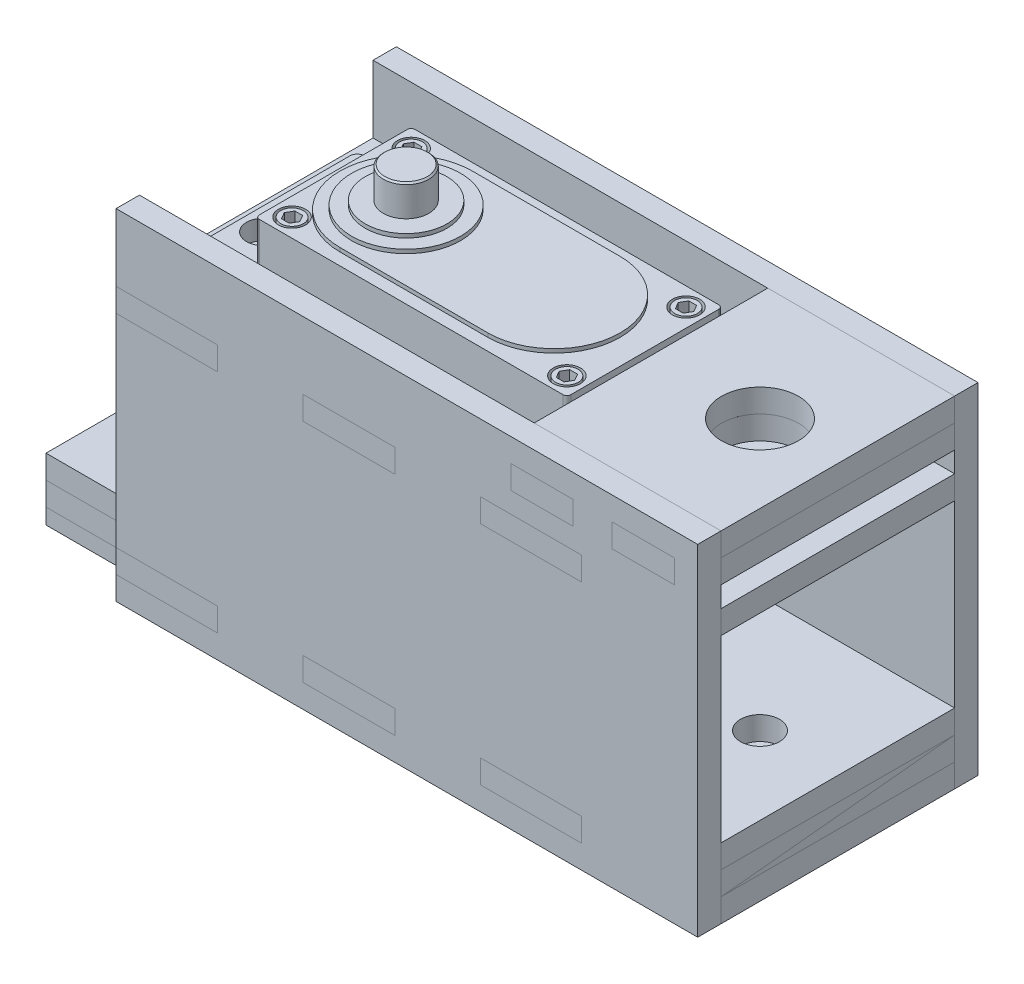
SolidWorks part; units mm, degrees
ref_plane "前视基准面" through (0, 0, 0) normal (0, 0, 1) x (1, 0, 0)
ref_plane "上视基准面" through (0, 0, 0) normal (0, 1, 0) x (1, 0, 0)
ref_plane "右视基准面" through (0, 0, 0) normal (1, 0, 0) x (0, 0, -1)
sketch "草图1" plane through (0, 0, 0) normal (0, 0, 1) x (1, 0, 0)
  line L1 (-20, -18.85) -> (20, -18.85)
  line L2 (-20, -18.85) -> (-20, 18.85)
  line L3 (-20, 18.85) -> (20, 18.85)
  line L4 (20, -18.85) -> (20, 18.85)
  line L5 (-20, -18.85) -> (20, 18.85) construction
  line L6 (-20, 18.85) -> (20, -18.85) construction
  point P0 (0, 0)
  dimension "D1" = 37.7
  dimension "D2" = 40
extrude "凸台-拉伸1" add sketch "草图1" along normal blind 20
sketch "草图2" plane through (0, 18.85, 0) normal (0, 1, 0) x (1, 0, 0)
  line L0 (-20, -20) -> (-20, 0) construction
  line L1 (20, 0) -> (-20, 0) construction
  line L2 (0, 0) -> (0, -4.2518) construction
  line L3 (20, -10) -> (9.0138, -10) construction
  line L4 (20, -20) -> (20, 0) construction
  circle A0 centre (-17.65, -2.35) radius 1.75
  circle A1 centre (17.65, -2.35) radius 1.75
  circle A2 centre (17.65, -17.65) radius 1.75
  circle A3 centre (-17.65, -17.65) radius 1.75
  dimension "D1" = 3.5
  dimension "D2" = 2.35
  dimension "D3" = 2.35
extrude "切除-拉伸1" cut sketch "草图2" against normal blind 1.5 contours A0 | A1 | A2 | A3
sketch "草图3" plane through (0, 17.35, 0) normal (0, 1, 0) x (1, 0, 0)
  line L0 (0, 0) -> (0, -10.9401) construction
  line L1 (-17.15, -1.484) -> (-18.15, -1.484)
  line L2 (-18.15, -1.484) -> (-18.65, -2.35)
  line L3 (-18.65, -2.35) -> (-18.15, -3.216)
  line L4 (-18.15, -3.216) -> (-17.15, -3.216)
  line L5 (-17.15, -3.216) -> (-16.65, -2.35)
  line L6 (-16.65, -2.35) -> (-17.15, -1.484)
  line L7 (20, 0) -> (-20, 0) construction
  line L8 (-20, -10) -> (-14.6951, -10) construction
  line L9 (-20, -20) -> (-20, 0) construction
  line L10 (-17.15, -18.516) -> (-18.15, -18.516)
  line L11 (-16.65, -17.65) -> (-17.15, -18.516)
  line L12 (-17.15, -16.784) -> (-16.65, -17.65)
  line L13 (-18.15, -16.784) -> (-17.15, -16.784)
  line L14 (-18.65, -17.65) -> (-18.15, -16.784)
  line L15 (-18.15, -18.516) -> (-18.65, -17.65)
  line L16 (16.65, -17.65) -> (17.15, -18.516)
  line L17 (17.15, -16.784) -> (16.65, -17.65)
  line L18 (18.15, -16.784) -> (17.15, -16.784)
  line L19 (18.65, -17.65) -> (18.15, -16.784)
  line L20 (18.15, -18.516) -> (18.65, -17.65)
  line L21 (17.15, -18.516) -> (18.15, -18.516)
  line L22 (16.65, -2.35) -> (17.15, -1.484)
  line L23 (17.15, -3.216) -> (16.65, -2.35)
  line L24 (17.15, -1.484) -> (18.15, -1.484)
  line L25 (18.15, -1.484) -> (18.65, -2.35)
  line L26 (18.65, -2.35) -> (18.15, -3.216)
  line L27 (18.15, -3.216) -> (17.15, -3.216)
  circle A2 centre (-17.65, -2.35) radius 1.45
  circle A3 centre (-17.65, -2.35) radius 1.45
  circle A4 centre (-17.65, -17.65) radius 1.45
  circle A5 centre (17.65, -2.35) radius 1.45
  circle A6 centre (17.65, -2.35) radius 1.45
  circle A7 centre (-17.65, -17.65) radius 1.45
  circle A8 centre (-17.65, -2.35) radius 0.866 construction
  circle A9 centre (17.65, -17.65) radius 1.45
  circle A10 centre (17.65, -17.65) radius 1.45
  dimension "D5" = 1
  dimension "D1" = 0.3
  dimension "D2" = 0.3
  dimension "D3" = 0.3
  dimension "D4" = 0.3
extrude "凸台-拉伸2" add sketch "草图3" along normal blind 1.5
sketch "草图4" plane through (0, 18.85, 0) normal (0, 1, 0) x (1, 0, 0)
  line L0 (-10.7, -9.95) -> (8.3, -9.95) construction
  line L1 (-10.7, -1.45) -> (8.3, -1.45)
  line L2 (-10.7, -18.45) -> (8.3, -18.45)
  line L3 (20, 0) -> (-20, 0) construction
  line L4 (20, -20) -> (-20, -20) construction
  line L5 (-20, -20) -> (-20, 0) construction
  arc A0 (-10.7, -1.45) -> (-10.7, -18.45) centre (-10.7, -9.95) ccw
  arc A1 (8.3, -18.45) -> (8.3, -1.45) centre (8.3, -9.95) ccw
  point P2 (-1.2, -9.95)
  dimension "D1" = 17
  dimension "D2" = 1.45
  dimension "D3" = 1.55
  dimension "D4" = 19
  dimension "D5" = 9.3
extrude "凸台-拉伸3" add sketch "草图4" along normal blind 0.5
sketch "草图5" plane through (0, 19.35, 0) normal (0, 1, 0) x (1, 0, 0)
  circle A0 centre (-10.7, -9.95) radius 7
  dimension "D1" = 14
extrude "凸台-拉伸4" add sketch "草图5" along normal blind 0.5
sketch "草图6" plane through (0, 19.85, 0) normal (0, 1, 0) x (1, 0, 0)
  circle A0 centre (-10.7, -9.95) radius 5.25
  dimension "D1" = 10.5
extrude "凸台-拉伸5" add sketch "草图6" along normal blind 0.5
sketch "草图7" plane through (0, 20.35, 0) normal (0, 1, 0) x (1, 0, 0)
  circle A0 centre (-10.7, -9.95) radius 2.925
  dimension "D1" = 5.85
extrude "凸台-拉伸6" add sketch "草图7" along normal blind 4
chamfer "倒角1" distance 0.2 angle 45 1 edges at (-10.7, 24.35, 12.875)
sketch "草图8" plane through (0, 0, 20) normal (0, 0, 1) x (1, 0, 0)
  line L0 (20, -18.85) -> (20, 18.85) construction
  line L1 (-26.9, 12.7) -> (26.9, 12.7)
  line L2 (-26.9, 12.7) -> (-26.9, 10.2)
  line L3 (-26.9, 10.2) -> (26.9, 10.2)
  line L4 (26.9, 12.7) -> (26.9, 10.2)
  line L5 (-20, 18.85) -> (-20, -18.85) construction
  dimension "D1" = 2.5
  dimension "D2" = 6.15
  dimension "D3" = 6.9
  dimension "D4" = 6.9
extrude "凸台-拉伸7" add sketch "草图8" against normal up to surface (20 mm away) up to face at (0, 0, 0)
ref_plane "基准面1" through (0, 0, 0) normal (0, 1, 0) x (1, 0, 0)
mirror "镜向1" about plane through (0, 0, 0) normal (0, 1, 0) of "凸台-拉伸2", "切除-拉伸1"
fillet "圆角1" radius 1 4 edges at (-26.9, 11.45, 20) (-26.9, 11.45, 0) (26.9, 11.45, 0) (26.9, 11.45, 20)
sketch "草图9" plane through (0, 12.7, 0) normal (0, 1, 0) x (1, 0, 0)
  line L0 (-20, -20) -> (-25.9, -20) construction
  line L1 (-20, 0) -> (-20, -20) construction
  line L2 (-20, 0) -> (-25.9, 0) construction
  line L3 (0, 0) -> (0, -21.9377) construction
  circle A0 centre (-24, -5) radius 2.15
  circle A1 centre (-24, -15) radius 2.15
  circle A2 centre (24, -15) radius 2.15
  circle A3 centre (24, -5) radius 2.15
  dimension "D1" = 4.3
  dimension "D2" = 4.3
  dimension "D3" = 5
  dimension "D4" = 4
  dimension "D5" = 5
  dimension "D6" = 4
extrude "切除-拉伸2" cut sketch "草图9" against normal blind 4 contours A1 | A0 | A2 | A3
fillet "圆角2" radius 0.5 8 edges at (-20, 15.775, 0) (20, 15.775, 0) (20, -4.325, 0) (-20, -4.325, 0) (-20, -4.325, 20) (-20, 15.775, 20) (20, -4.325, 20) (20, 15.775, 20)
sketch "草图10" plane through (0, 10.2, 0) normal (0, -1, 0) x (1, 0, 0)
  line L0 (-19.5, 20) -> (19.5, 20) construction
  line L1 (-41.9, -5) -> (41.9, -5)
  line L2 (-41.9, -5) -> (-41.9, 25)
  line L3 (-41.9, 25) -> (41.9, 25)
  line L4 (41.9, -5) -> (41.9, 25)
  line L5 (-41.9, -5) -> (41.9, 25) construction
  line L6 (-41.9, 25) -> (41.9, -5) construction
  line L7 (-19.5, 0) -> (19.5, 0) construction
  line L8 (-26.9, 1) -> (-26.9, 19) construction
  line L9 (26.9, 1) -> (26.9, 19) construction
  line L10 (20, 19.5) -> (20, 0.5) construction
  line L11 (-20, 19.5) -> (-20, 0.5) construction
  line L12 (20, 19.5) -> (20, 0.5)
  line L13 (-19.5, 0) -> (19.5, 0)
  line L14 (-20, 19.5) -> (-20, 0.5)
  line L15 (-19.5, 20) -> (19.5, 20)
  arc A8 (20, 19.5) -> (19.5, 20) centre (19.5, 19.5) ccw construction
  arc A9 (19.5, 0) -> (20, 0.5) centre (19.5, 0.5) ccw construction
  arc A10 (-20, 0.5) -> (-19.5, 0) centre (-19.5, 0.5) ccw construction
  arc A11 (-19.5, 20) -> (-20, 19.5) centre (-19.5, 19.5) ccw construction
  arc A12 (20, 19.5) -> (19.5, 20) centre (19.5, 19.5) ccw
  arc A13 (19.5, 0) -> (20, 0.5) centre (19.5, 0.5) ccw
  arc A14 (-20, 0.5) -> (-19.5, 0) centre (-19.5, 0.5) ccw
  arc A15 (-19.5, 20) -> (-20, 19.5) centre (-19.5, 19.5) ccw
  circle A16 centre (-24, 15) radius 1.25
  circle A17 centre (-24, 5) radius 1.25
  circle A18 centre (24, 5) radius 1.25
  circle A19 centre (24, 15) radius 1.25
  point P0 (0, 10)
  dimension "D5" = 2.5
  dimension "D6" = 2.5
  dimension "D7" = 2.5
  dimension "D8" = 2.5
  dimension "D1" = 5
  dimension "D2" = 5
  dimension "D3" = 15
  dimension "D4" = 15
extrude "凸台-拉伸8" add sketch "草图10" along normal blind 3 separate body
sketch "草图11" plane through (0, 0, -5) normal (0, 0, -1) x (-1, 0, 0)
  line L0 (41.9, 10.2) -> (-41.9, 10.2) construction
  line L1 (-29.9, 10.2) -> (-16.9, 10.2)
  line L2 (-29.9, 10.2) -> (-29.9, 7.2)
  line L3 (-29.9, 7.2) -> (-16.9, 7.2)
  line L4 (-16.9, 10.2) -> (-16.9, 7.2)
  line L5 (41.9, 7.2) -> (-41.9, 7.2) construction
  line L6 (-41.9, 7.2) -> (-41.9, 10.2) construction
  line L11 (16.9, 10.2) -> (29.9, 10.2)
  line L12 (16.9, 10.2) -> (16.9, 7.2)
  line L13 (16.9, 7.2) -> (29.9, 7.2)
  line L14 (29.9, 10.2) -> (29.9, 7.2)
  line L15 (-5.9, 10.2) -> (5.9, 10.2)
  line L16 (-5.9, 10.2) -> (-5.9, 7.2)
  line L17 (-5.9, 7.2) -> (5.9, 7.2)
  line L18 (5.9, 10.2) -> (5.9, 7.2)
  line L19 (41.9, 7.2) -> (41.9, 10.2) construction
  dimension "D1" = 13
  dimension "D2" = 11
  dimension "D3" = 13
  dimension "D4" = 12
  dimension "D5" = 12
  dimension "D6" = 11
extrude "凸台-拉伸9" add sketch "草图11" along normal blind 3
ref_plane "基准面2" through (0, 0, 10) normal (0, 0, -1) x (-1, 0, 0)
mirror "镜向2" about plane through (0, 0, 10) normal (0, 0, -1) of "凸台-拉伸9"
sketch "草图14" plane through (0, 0, -5) normal (0, 0, -1) x (-1, 0, 0)
  line L0 (41.9, 7.2) -> (41.9, 10.2) construction
  line L1 (-41.9, 18.85) -> (41.9, 18.85)
  line L2 (-41.9, 18.85) -> (-41.9, -23.85)
  line L3 (-41.9, -23.85) -> (41.9, -23.85)
  line L4 (41.9, 18.85) -> (41.9, -23.85)
  line L5 (-19.5, 18.85) -> (19.5, 18.85) construction
  line L6 (-41.9, 7.2) -> (-41.9, 10.2) construction
  line L7 (16.9, 10.2) -> (16.9, 7.2) construction
  line L8 (16.9, 7.2) -> (29.9, 7.2) construction
  line L9 (29.9, 7.2) -> (29.9, 10.2) construction
  line L10 (29.9, 10.2) -> (16.9, 10.2) construction
  line L11 (-5.9, 10.2) -> (-5.9, 7.2) construction
  line L12 (-5.9, 7.2) -> (5.9, 7.2) construction
  line L13 (5.9, 7.2) -> (5.9, 10.2) construction
  line L14 (5.9, 10.2) -> (-5.9, 10.2) construction
  line L15 (-29.9, 10.2) -> (-29.9, 7.2) construction
  line L16 (-29.9, 7.2) -> (-16.9, 7.2) construction
  line L17 (-16.9, 7.2) -> (-16.9, 10.2) construction
  line L18 (-16.9, 10.2) -> (-29.9, 10.2) construction
  line L19 (16.9, 10.2) -> (16.9, 7.2)
  line L20 (16.9, 7.2) -> (29.9, 7.2)
  line L21 (29.9, 7.2) -> (29.9, 10.2)
  line L22 (29.9, 10.2) -> (16.9, 10.2)
  line L23 (-5.9, 10.2) -> (-5.9, 7.2)
  line L24 (-5.9, 7.2) -> (5.9, 7.2)
  line L25 (5.9, 7.2) -> (5.9, 10.2)
  line L26 (5.9, 10.2) -> (-5.9, 10.2)
  line L27 (-29.9, 10.2) -> (-29.9, 7.2)
  line L28 (-29.9, 7.2) -> (-16.9, 7.2)
  line L29 (-16.9, 7.2) -> (-16.9, 10.2)
  line L30 (-16.9, 10.2) -> (-29.9, 10.2)
  line L31 (19.5, -18.85) -> (-19.5, -18.85) construction
  dimension "D1" = 0
  dimension "D2" = 0
  dimension "D3" = 0
  dimension "D4" = 5
extrude "凸台-拉伸10" add sketch "草图14" along normal blind 3 separate body
mirror "镜向3" about plane through (0, 0, 10) normal (0, 0, -1) of bodies 119
sketch "草图15" plane through (41.9, 0, 0) normal (1, 0, 0) x (0, 0, -1)
  line L4 (5, 10.2) -> (-25, 10.2)
  line L5 (-25, 10.2) -> (-25, 7.2)
  line L6 (-25, 7.2) -> (5, 7.2)
  line L7 (5, 7.2) -> (5, 10.2)
  line L8 (5, 10.2) -> (-25, 10.2)
  line L9 (-25, 10.2) -> (-25, 7.2)
  line L10 (-25, 7.2) -> (5, 7.2)
  line L11 (5, 7.2) -> (5, 10.2)
  dimension "D1" = 0
extrude "凸台-拉伸11" add sketch "草图15" along normal blind 15
sketch "草图16" plane through (41.9, 0, 0) normal (1, 0, 0) x (0, 0, -1)
  line L4 (5, 18.85) -> (5, -23.85)
  line L5 (5, -23.85) -> (8, -23.85)
  line L6 (8, -23.85) -> (8, 18.85)
  line L7 (8, 18.85) -> (5, 18.85)
  line L8 (5, 18.85) -> (5, -23.85)
  line L9 (5, -23.85) -> (8, -23.85)
  line L10 (8, -23.85) -> (8, 18.85)
  line L11 (8, 18.85) -> (5, 18.85)
  dimension "D1" = 0
extrude "凸台-拉伸12" add sketch "草图16" along normal up to surface (15 mm away) up to face at (56.9, 8.7, 10)
sketch "草图17" plane through (41.9, 0, 0) normal (1, 0, 0) x (0, 0, -1)
  line L4 (-25, -23.85) -> (-25, 18.85)
  line L5 (-25, 18.85) -> (-28, 18.85)
  line L6 (-28, 18.85) -> (-28, -23.85)
  line L7 (-28, -23.85) -> (-25, -23.85)
  line L8 (-25, -23.85) -> (-25, 18.85)
  line L9 (-25, 18.85) -> (-28, 18.85)
  line L10 (-28, 18.85) -> (-28, -23.85)
  line L11 (-28, -23.85) -> (-25, -23.85)
  dimension "D1" = 0
extrude "凸台-拉伸13" add sketch "草图17" along normal up to surface (15 mm away) up to face at (56.9, 8.7, 10)
sketch "草图18" plane through (0, 10.2, 0) normal (0, 1, 0) x (1, 0, 0)
  line L0 (26.9, -1) -> (26.9, -19) construction
  circle A0 centre (52.3, -10) radius 2.5
  dimension "D2" = 5
  dimension "D1" = 25.4
extrude "切除-拉伸3" cut sketch "草图18" against normal blind 15
sketch "草图19" plane through (0, 18.85, 0) normal (0, 1, 0) x (1, 0, 0)
  line L0 (29.9, 5) -> (56.9, 5) construction
  line L1 (56.9, 8) -> (31.9, 8)
  line L2 (56.9, 8) -> (56.9, 5)
  line L3 (56.9, 5) -> (31.9, 5)
  line L4 (31.9, 8) -> (31.9, 5)
  dimension "D1" = 25
extrude "凸台-拉伸14" add sketch "草图19" along normal blind 8
sketch "草图20" plane through (0, 18.85, 0) normal (0, 1, 0) x (1, 0, 0)
  line L0 (56.9, -25) -> (29.9, -25) construction
  line L1 (31.9, -25) -> (56.9, -25)
  line L2 (31.9, -25) -> (31.9, -28)
  line L3 (31.9, -28) -> (56.9, -28)
  line L4 (56.9, -25) -> (56.9, -28)
extrude "凸台-拉伸15" add sketch "草图20" along normal up to surface (8 mm away) up to face at (44.4, 26.85, -6.5)
sketch "草图21" plane through (56.9, 0, 0) normal (1, 0, 0) x (0, 0, -1)
  line L0 (-25, 26.85) -> (-28, 26.85) construction
  line L1 (-25, 26.85) -> (5, 26.85)
  line L2 (-25, 26.85) -> (-25, 23.85)
  line L3 (-25, 23.85) -> (5, 23.85)
  line L4 (5, 26.85) -> (5, 23.85)
  line L5 (5, 26.85) -> (5, -23.85) construction
  dimension "D1" = 3
extrude "凸台-拉伸16" add sketch "草图21" against normal up to surface (25 mm away) separate body up to face at (31.9, 22.85, 26.5)
sketch "草图22" plane through (0, 23.85, 0) normal (0, -1, 0) x (1, 0, 0)
  circle A0 centre (52.3, 10) radius 2.5 construction
  circle A1 centre (52.3, 10) radius 2.5
extrude "切除-拉伸4" cut sketch "草图22" against normal blind 10
sketch "草图23" plane through (0, 26.85, 0) normal (0, 1, 0) x (1, 0, 0)
  line L0 (12.837, -10) -> (-55.6494, -10) construction
  line L2 (56.9, -28) -> (31.9, -28) construction
  line L3 (56.9, 8) -> (31.9, 8) construction
  line L4 (56.9, -28) -> (47.6466, -28)
  line L5 (56.9, 8) -> (47.6466, 8)
  line L6 (56.9, 8) -> (79.2685, 8)
  line L7 (79.2685, 8) -> (56.9, -28)
  arc A0 (47.6466, -28) -> (47.6466, 8) centre (34.8957, -10) ccw
extrude "切除-拉伸5" cut sketch "草图23" against normal blind 100
sketch "草图25" plane through (0, -18.85, 0) normal (0, -1, 0) x (1, 0, 0)
  line L0 (-20, 19.5) -> (-20, 0.5) construction
  line L1 (-41.9, 25) -> (51.0693, 25)
  line L2 (-41.9, 25) -> (-41.9, -5)
  line L3 (-41.9, -5) -> (51.0693, -5)
  line L4 (51.0693, 25) -> (51.0693, -5)
  line L5 (-19.5, 20) -> (19.5, 20) construction
  line L6 (20, 19.5) -> (20, 0.5) construction
  line L7 (-19.5, 0) -> (19.5, 0) construction
  line L8 (-20, 19.5) -> (-20, 0.5)
  line L9 (-19.5, 20) -> (19.5, 20)
  line L10 (20, 19.5) -> (20, 0.5)
  line L11 (-19.5, 0) -> (19.5, 0)
  arc A0 (-20, 0.5) -> (-19.5, 0) centre (-19.5, 0.5) ccw construction
  arc A1 (-19.5, 20) -> (-20, 19.5) centre (-19.5, 19.5) ccw construction
  arc A2 (20, 19.5) -> (19.5, 20) centre (19.5, 19.5) ccw construction
  arc A3 (19.5, 0) -> (20, 0.5) centre (19.5, 0.5) ccw construction
  arc A4 (-20, 0.5) -> (-19.5, 0) centre (-19.5, 0.5) ccw
  arc A5 (-19.5, 20) -> (-20, 19.5) centre (-19.5, 19.5) ccw
  arc A6 (20, 19.5) -> (19.5, 20) centre (19.5, 19.5) ccw
  arc A7 (19.5, 0) -> (20, 0.5) centre (19.5, 0.5) ccw
extrude "凸台-拉伸17" add sketch "草图25" against normal blind 3 separate body
sketch "草图26" plane through (0, -18.85, 0) normal (0, -1, 0) x (1, 0, 0)
  line L0 (56.9, 11.5478) -> (56.9, 8.4522) construction
  line L1 (56.9, 11.5478) -> (56.9, 8.4522)
  line L2 (51.0693, -5) -> (51.0693, 25) construction
  line L3 (51.0693, -5) -> (51.0693, 25)
  arc A0 (51.0693, -5) -> (56.9, 8.4522) centre (34.8957, 10) ccw construction
  arc A1 (51.0693, -5) -> (56.9, 8.4522) centre (34.8957, 10) ccw
  arc A2 (56.9, 11.5478) -> (51.0693, 25) centre (34.8957, 10) ccw construction
  arc A3 (56.9, 11.5478) -> (51.0693, 25) centre (34.8957, 10) ccw
extrude "凸台-拉伸18" add sketch "草图26" against normal blind 3
sketch "草图27" plane through (0, -15.85, 0) normal (0, 1, 0) x (1, 0, 0)
  circle A0 centre (52.3, -10) radius 2.5 construction
  circle A1 centre (52.3, -10) radius 2.5
extrude "切除-拉伸6" cut sketch "草图27" against normal blind 3
sketch "草图28" plane through (0, -18.85, 0) normal (0, -1, 0) x (1, 0, 0)
  line L4 (-41.9, 25) -> (-41.9, -5)
  line L5 (-41.9, -5) -> (51.0693, -5)
  line L6 (56.9, 8.4522) -> (56.9, 11.5478)
  line L7 (51.0693, 25) -> (-41.9, 25)
  line L8 (-41.9, 25) -> (-41.9, -5)
  line L9 (-41.9, -5) -> (51.0693, -5)
  line L10 (56.9, 8.4522) -> (56.9, 11.5478)
  line L11 (51.0693, 25) -> (-41.9, 25)
  arc A2 (51.0693, -5) -> (56.9, 8.4522) centre (34.8957, 10) ccw
  arc A3 (56.9, 11.5478) -> (51.0693, 25) centre (34.8957, 10) ccw
  arc A4 (51.0693, -5) -> (56.9, 8.4522) centre (34.8957, 10) ccw
  arc A5 (56.9, 11.5478) -> (51.0693, 25) centre (34.8957, 10) ccw
  dimension "D1" = 0
extrude "凸台-拉伸19" add sketch "草图28" along normal up to surface (5 mm away) separate body
sketch "草图29" plane through (0, -18.85, 0) normal (0, 1, 0) x (1, 0, 0)
  circle A0 centre (52.3, -10) radius 2.5 construction
  circle A1 centre (52.3, -10) radius 2.5
extrude "切除-拉伸7" cut sketch "草图29" against normal blind 13
sketch "草图30" plane through (0, 26.85, 0) normal (0, 1, 0) x (1, 0, 0)
  line L2 (34.8, 20.7576) -> (34.8, -40.7576)
  line L3 (34.8, -40.7576) -> (61.8691, -40.7576)
  line L5 (34.8, 20.7576) -> (61.8691, 20.7576)
  line L6 (61.8691, -40.7576) -> (61.8691, 20.7576)
extrude "切除-拉伸8" cut sketch "草图30" against normal blind 76
sketch "草图31" plane through (34.8, 0, 0) normal (1, 0, 0) x (0, 0, -1)
  line L4 (-25, 26.85) -> (-25, 23.85)
  line L5 (-25, 23.85) -> (5, 23.85)
  line L6 (5, 23.85) -> (5, 26.85)
  line L7 (5, 26.85) -> (-25, 26.85)
  line L8 (-25, 26.85) -> (-25, 23.85)
  line L9 (-25, 23.85) -> (5, 23.85)
  line L10 (5, 23.85) -> (5, 26.85)
  line L11 (5, 26.85) -> (-25, 26.85)
  dimension "D1" = 0
extrude "凸台-拉伸20" add sketch "草图31" along normal blind 10
sketch "草图32" plane through (34.8, 0, 0) normal (1, 0, 0) x (0, 0, -1)
  line L4 (8, -23.85) -> (8, 26.85)
  line L5 (8, 26.85) -> (5, 26.85)
  line L6 (5, 26.85) -> (5, -23.85)
  line L7 (5, -23.85) -> (8, -23.85)
  line L8 (8, -23.85) -> (8, 26.85)
  line L9 (8, 26.85) -> (5, 26.85)
  line L10 (5, 26.85) -> (5, -23.85)
  line L11 (5, -23.85) -> (8, -23.85)
  dimension "D1" = 0
extrude "凸台-拉伸21" add sketch "草图32" along normal blind 10
sketch "草图33" plane through (34.8, 0, 0) normal (1, 0, 0) x (0, 0, -1)
  line L4 (-28, 26.85) -> (-28, -23.85)
  line L5 (-28, -23.85) -> (-25, -23.85)
  line L6 (-25, -23.85) -> (-25, 26.85)
  line L7 (-25, 26.85) -> (-28, 26.85)
  line L8 (-28, 26.85) -> (-28, -23.85)
  line L9 (-28, -23.85) -> (-25, -23.85)
  line L10 (-25, -23.85) -> (-25, 26.85)
  line L11 (-25, 26.85) -> (-28, 26.85)
  dimension "D1" = 0
extrude "凸台-拉伸22" add sketch "草图33" along normal blind 10
sketch "草图34" plane through (34.8, 0, 0) normal (1, 0, 0) x (0, 0, -1)
  line L4 (-25, 7.2) -> (5, 7.2)
  line L5 (5, 7.2) -> (5, 10.2)
  line L6 (5, 10.2) -> (-25, 10.2)
  line L7 (-25, 10.2) -> (-25, 7.2)
  line L8 (-25, 7.2) -> (5, 7.2)
  line L9 (5, 7.2) -> (5, 10.2)
  line L10 (5, 10.2) -> (-25, 10.2)
  line L11 (-25, 10.2) -> (-25, 7.2)
  dimension "D1" = 0
extrude "凸台-拉伸23" add sketch "草图34" along normal up to surface (10 mm away) up to face at (44.8, 25.35, 10)
sketch "草图35" plane through (34.8, 0, 0) normal (1, 0, 0) x (0, 0, -1)
  line L4 (-25, -15.85) -> (-25, -18.85)
  line L5 (-25, -18.85) -> (5, -18.85)
  line L6 (5, -18.85) -> (5, -15.85)
  line L7 (5, -15.85) -> (-25, -15.85)
  line L8 (-25, -15.85) -> (-25, -18.85)
  line L9 (-25, -18.85) -> (5, -18.85)
  line L10 (5, -18.85) -> (5, -15.85)
  line L11 (5, -15.85) -> (-25, -15.85)
  dimension "D1" = 0
extrude "凸台-拉伸24" add sketch "草图35" along normal blind 10
sketch "草图36" plane through (0, 26.85, 0) normal (0, 1, 0) x (1, 0, 0)
  line L0 (26.9, -10) -> (34.8, -10)
  line L1 (26.9, -1) -> (26.9, -19) construction
  circle A0 centre (34.8, -10) radius 2.5
  dimension "D2" = 5
  dimension "D1" = 7.9
extrude "切除-拉伸9" cut sketch "草图36" against normal blind 90 contours A0 region at (34.8, 26.85, 12.4293)
sketch "草图37" plane through (0, -18.85, 0) normal (0, -1, 0) x (1, 0, 0)
  line L4 (-41.9, -5) -> (44.8, -5)
  line L5 (44.8, -5) -> (44.8, 25)
  line L6 (44.8, 25) -> (-41.9, 25)
  line L7 (-41.9, 25) -> (-41.9, -5)
  line L8 (-41.9, -5) -> (44.8, -5)
  line L9 (44.8, -5) -> (44.8, 25)
  line L10 (44.8, 25) -> (-41.9, 25)
  line L11 (-41.9, 25) -> (-41.9, -5)
  dimension "D1" = 0
extrude "凸台-拉伸25" add sketch "草图37" along normal blind 3 separate body
sketch "草图38" plane through (0, -23.85, 0) normal (0, -1, 0) x (1, 0, 0)
  line L4 (-41.9, -8) -> (44.8, -8)
  line L5 (44.8, -8) -> (44.8, -5)
  line L6 (44.8, -5) -> (-41.9, -5)
  line L7 (-41.9, -5) -> (-41.9, -8)
  line L8 (-41.9, -8) -> (44.8, -8)
  line L9 (44.8, -8) -> (44.8, -5)
  line L10 (44.8, -5) -> (-41.9, -5)
  line L11 (-41.9, -5) -> (-41.9, -8)
  dimension "D1" = 0
extrude "凸台-拉伸26" add sketch "草图38" along normal blind 1
sketch "草图39" plane through (0, -23.85, 0) normal (0, -1, 0) x (1, 0, 0)
  line L4 (-41.9, 25) -> (44.8, 25)
  line L5 (44.8, 25) -> (44.8, 28)
  line L6 (44.8, 28) -> (-41.9, 28)
  line L7 (-41.9, 28) -> (-41.9, 25)
  line L8 (-41.9, 25) -> (44.8, 25)
  line L9 (44.8, 25) -> (44.8, 28)
  line L10 (44.8, 28) -> (-41.9, 28)
  line L11 (-41.9, 28) -> (-41.9, 25)
  dimension "D1" = 0
extrude "凸台-拉伸27" add sketch "草图39" along normal blind 1
sketch "草图40" plane through (0, 0, 28) normal (0, 0, 1) x (1, 0, 0)
  line L0 (-29.9, -18.85) -> (-16.9, -18.85)
  line L1 (-16.9, -18.85) -> (-16.9, -21.85)
  line L2 (-16.9, -21.85) -> (-29.9, -21.85)
  line L3 (-29.9, -21.85) -> (-29.9, -18.85)
  line L4 (-5.9, -18.85) -> (-5.9, -21.85)
  line L5 (-5.9, -21.85) -> (5.9, -21.85)
  line L6 (5.9, -21.85) -> (5.9, -18.85)
  line L7 (5.9, -18.85) -> (-5.9, -18.85)
  line L8 (16.9, -18.85) -> (29.9, -18.85)
  line L9 (29.9, -18.85) -> (29.9, -21.85)
  line L10 (29.9, -21.85) -> (16.9, -21.85)
  line L11 (16.9, -21.85) -> (16.9, -18.85)
  line L12 (44.8, -24.85) -> (-41.9, -24.85) construction
  dimension "D1" = 3
  dimension "D2" = 3
  dimension "D3" = 3
  dimension "D4" = 3
  dimension "D5" = 3
  dimension "D6" = 13
  dimension "D7" = 3
extrude "切除-拉伸10" cut sketch "草图40" against normal blind 45
sketch "草图41" plane through (0, 0, -5) normal (0, 0, 1) x (1, 0, 0)
  line L4 (29.9, -18.85) -> (16.9, -18.85)
  line L5 (29.9, -21.85) -> (29.9, -18.85)
  line L6 (16.9, -21.85) -> (29.9, -21.85)
  line L7 (16.9, -18.85) -> (16.9, -21.85)
  line L8 (29.9, -18.85) -> (16.9, -18.85)
  line L9 (29.9, -21.85) -> (29.9, -18.85)
  line L10 (16.9, -21.85) -> (29.9, -21.85)
  line L11 (16.9, -18.85) -> (16.9, -21.85)
  line L12 (-5.9, -18.85) -> (-5.9, -21.85)
  line L13 (-5.9, -21.85) -> (5.9, -21.85)
  line L14 (5.9, -21.85) -> (5.9, -18.85)
  line L15 (5.9, -18.85) -> (-5.9, -18.85)
  line L16 (-5.9, -18.85) -> (-5.9, -21.85)
  line L17 (-5.9, -21.85) -> (5.9, -21.85)
  line L18 (5.9, -21.85) -> (5.9, -18.85)
  line L19 (5.9, -18.85) -> (-5.9, -18.85)
  line L20 (-16.9, -18.85) -> (-29.9, -18.85)
  line L21 (-16.9, -21.85) -> (-16.9, -18.85)
  line L22 (-29.9, -21.85) -> (-16.9, -21.85)
  line L23 (-29.9, -18.85) -> (-29.9, -21.85)
  line L24 (-16.9, -18.85) -> (-29.9, -18.85)
  line L25 (-16.9, -21.85) -> (-16.9, -18.85)
  line L26 (-29.9, -21.85) -> (-16.9, -21.85)
  line L27 (-29.9, -18.85) -> (-29.9, -21.85)
  dimension "D1" = 0
  dimension "D2" = 0
  dimension "D3" = 0
extrude "切除-拉伸11" cut sketch "草图41" against normal blind 59
sketch "草图42" plane through (0, -18.85, 0) normal (0, -1, 0) x (1, 0, 0)
  line L28 (29.9, -5) -> (44.8, -5)
  line L29 (44.8, -5) -> (44.8, 25)
  line L30 (44.8, 25) -> (29.9, 25)
  line L31 (29.9, 25) -> (29.9, 28)
  line L32 (29.9, 28) -> (16.9, 28)
  line L33 (16.9, 28) -> (16.9, 25)
  line L34 (16.9, 25) -> (5.9, 25)
  line L35 (5.9, 25) -> (5.9, 28)
  line L36 (5.9, 28) -> (-5.9, 28)
  line L37 (-5.9, 28) -> (-5.9, 25)
  line L38 (-5.9, 25) -> (-16.9, 25)
  line L39 (-16.9, 25) -> (-16.9, 28)
  line L40 (-16.9, 28) -> (-29.9, 28)
  line L41 (-29.9, 28) -> (-29.9, 25)
  line L42 (-29.9, 25) -> (-41.9, 25)
  line L43 (-41.9, 25) -> (-41.9, -5)
  line L44 (-41.9, -5) -> (-29.9, -5)
  line L45 (-29.9, -5) -> (-29.9, -8)
  line L46 (-29.9, -8) -> (-16.9, -8)
  line L47 (-16.9, -8) -> (-16.9, -5)
  line L48 (-16.9, -5) -> (-5.9, -5)
  line L49 (-5.9, -5) -> (-5.9, -8)
  line L50 (-5.9, -8) -> (5.9, -8)
  line L51 (5.9, -8) -> (5.9, -5)
  line L52 (5.9, -5) -> (16.9, -5)
  line L53 (16.9, -5) -> (16.9, -8)
  line L54 (16.9, -8) -> (29.9, -8)
  line L55 (29.9, -8) -> (29.9, -5)
  line L56 (29.9, -5) -> (44.8, -5)
  line L57 (44.8, -5) -> (44.8, 25)
  line L58 (44.8, 25) -> (29.9, 25)
  line L59 (29.9, 25) -> (29.9, 28)
  line L60 (29.9, 28) -> (16.9, 28)
  line L61 (16.9, 28) -> (16.9, 25)
  line L62 (16.9, 25) -> (5.9, 25)
  line L63 (5.9, 25) -> (5.9, 28)
  line L64 (5.9, 28) -> (-5.9, 28)
  line L65 (-5.9, 28) -> (-5.9, 25)
  line L66 (-5.9, 25) -> (-16.9, 25)
  line L67 (-16.9, 25) -> (-16.9, 28)
  line L68 (-16.9, 28) -> (-29.9, 28)
  line L69 (-29.9, 28) -> (-29.9, 25)
  line L70 (-29.9, 25) -> (-41.9, 25)
  line L71 (-41.9, 25) -> (-41.9, -5)
  line L72 (-41.9, -5) -> (-29.9, -5)
  line L73 (-29.9, -5) -> (-29.9, -8)
  line L74 (-29.9, -8) -> (-16.9, -8)
  line L75 (-16.9, -8) -> (-16.9, -5)
  line L76 (-16.9, -5) -> (-5.9, -5)
  line L77 (-5.9, -5) -> (-5.9, -8)
  line L78 (-5.9, -8) -> (5.9, -8)
  line L79 (5.9, -8) -> (5.9, -5)
  line L80 (5.9, -5) -> (16.9, -5)
  line L81 (16.9, -5) -> (16.9, -8)
  line L82 (16.9, -8) -> (29.9, -8)
  line L83 (29.9, -8) -> (29.9, -5)
  dimension "D1" = 0
extrude "凸台-拉伸28" add sketch "草图42" along normal blind 3 separate body
sketch "草图43" plane through (31.9, 0, 0) normal (-1, 0, 0) x (0, 0, 1)
  line L4 (-8, 18.85) -> (-5, 18.85)
  line L5 (-5, 18.85) -> (-5, 26.85)
  line L6 (-5, 26.85) -> (-8, 26.85)
  line L7 (-8, 26.85) -> (-8, 18.85)
  line L8 (-8, 18.85) -> (-5, 18.85)
  line L9 (-5, 18.85) -> (-5, 26.85)
  line L10 (-5, 26.85) -> (-8, 26.85)
  line L11 (-8, 26.85) -> (-8, 18.85)
  dimension "D1" = 0
extrude "凸台-拉伸29" add sketch "草图43" along normal blind 3
sketch "草图44" plane through (31.9, 0, 0) normal (-1, 0, 0) x (0, 0, 1)
  line L4 (28, 18.85) -> (28, 26.85)
  line L5 (28, 26.85) -> (25, 26.85)
  line L6 (25, 26.85) -> (25, 18.85)
  line L7 (25, 18.85) -> (28, 18.85)
  line L8 (28, 18.85) -> (28, 26.85)
  line L9 (28, 26.85) -> (25, 26.85)
  line L10 (25, 26.85) -> (25, 18.85)
  line L11 (25, 18.85) -> (28, 18.85)
  dimension "D1" = 0
extrude "凸台-拉伸30" add sketch "草图44" along normal blind 3
sketch "草图45" plane through (31.9, 0, 0) normal (-1, 0, 0) x (0, 0, 1)
  line L4 (25, 23.85) -> (25, 26.85)
  line L5 (25, 26.85) -> (-5, 26.85)
  line L6 (-5, 26.85) -> (-5, 23.85)
  line L7 (-5, 23.85) -> (25, 23.85)
  line L8 (25, 23.85) -> (25, 26.85)
  line L9 (25, 26.85) -> (-5, 26.85)
  line L10 (-5, 26.85) -> (-5, 23.85)
  line L11 (-5, 23.85) -> (25, 23.85)
  dimension "D1" = 0
extrude "凸台-拉伸31" add sketch "草图45" along normal blind 3
sketch "草图46" plane through (0, 26.85, 0) normal (0, 1, 0) x (1, 0, 0)
  line L4 (28.9, 5) -> (44.8, 5)
  line L5 (44.8, 5) -> (44.8, 8)
  line L6 (44.8, 8) -> (28.9, 8)
  line L7 (28.9, 8) -> (28.9, 5)
  line L8 (28.9, 5) -> (44.8, 5)
  line L9 (44.8, 5) -> (44.8, 8)
  line L10 (44.8, 8) -> (28.9, 8)
  line L11 (28.9, 8) -> (28.9, 5)
  dimension "D1" = 0
sketch "草图47" plane through (0, 26.85, 0) normal (0, 1, 0) x (1, 0, 0)
  line L4 (28.9, -28) -> (44.8, -28)
  line L5 (44.8, -28) -> (44.8, -25)
  line L6 (44.8, -25) -> (28.9, -25)
  line L7 (28.9, -25) -> (28.9, -28)
  line L8 (28.9, -28) -> (44.8, -28)
  line L9 (44.8, -28) -> (44.8, -25)
  line L10 (44.8, -25) -> (28.9, -25)
  line L11 (28.9, -25) -> (28.9, -28)
  dimension "D1" = 0
sketch "草图50" plane through (-41.9, 0, 0) normal (-1, 0, 0) x (0, 0, 1)
  line L1 (-14.2479, -30.4832) -> (35.7509, -30.4832)
  line L2 (-14.2479, -30.4832) -> (-14.2479, 30.4832)
  line L3 (-14.2479, 30.4832) -> (35.7509, 30.4832)
  line L4 (35.7509, -30.4832) -> (35.7509, 30.4832)
  line L5 (-14.2479, -30.4832) -> (35.7509, 30.4832) construction
  line L6 (-14.2479, 30.4832) -> (35.7509, -30.4832) construction
  point P0 (10.7515, 0)
extrude "切除-拉伸12" cut sketch "草图50" against normal blind 12
sketch "草图51" plane through (0, 26.85, 0) normal (0, 1, 0) x (1, 0, 0)
  circle A0 centre (34.8, -10) radius 4.95
  dimension "D1" = 9.9
extrude "切除-拉伸13" cut sketch "草图51" against normal blind 66
sketch "草图52" plane through (28.9, 0, 0) normal (-1, 0, 0) x (0, 0, 1)
  line L4 (-5, 23.85) -> (25, 23.85)
  line L5 (25, 23.85) -> (25, 26.85)
  line L6 (25, 26.85) -> (-5, 26.85)
  line L7 (-5, 26.85) -> (-5, 23.85)
  line L8 (-5, 23.85) -> (25, 23.85)
  line L9 (25, 23.85) -> (25, 26.85)
  line L10 (25, 26.85) -> (-5, 26.85)
  line L11 (-5, 26.85) -> (-5, 23.85)
  dimension "D1" = 0
extrude "凸台-拉伸36" add sketch "草图52" along normal blind 2
sketch "草图53" plane through (0, 26.85, 0) normal (0, 1, 0) x (1, 0, 0)
  line L1 (22.1858, -35.4654) -> (48.7438, -35.4654)
  line L2 (22.1858, -35.4654) -> (22.1858, 12.4959)
  line L3 (22.1858, 12.4959) -> (48.7438, 12.4959)
  line L4 (48.7438, -35.4654) -> (48.7438, 12.4959)
  line L5 (22.1858, -35.4654) -> (48.7438, 12.4959) construction
  line L6 (22.1858, 12.4959) -> (48.7438, -35.4654) construction
  point P0 (35.4648, -11.4848)
extrude "切除-拉伸14" cut sketch "草图53" against normal up to surface (8 mm away) up to face at (-0.5, 18.85, 26.5)
sketch "草图54" plane through (0, 18.85, 0) normal (0, 1, 0) x (1, 0, 0)
  line L0 (16.9, 5) -> (29.9, 5) construction
  line L1 (44.8, 8) -> (29.8, 8)
  line L2 (44.8, 8) -> (44.8, 5)
  line L3 (44.8, 5) -> (29.8, 5)
  line L4 (29.8, 8) -> (29.8, 5)
  line L6 (44.8, -28) -> (29.8, -28)
  line L7 (44.8, -28) -> (44.8, -25)
  line L8 (44.8, -25) -> (29.8, -25)
  line L9 (29.8, -28) -> (29.8, -25)
  dimension "D1" = 15
  dimension "D2" = 15
  dimension "D3" = 3
extrude "凸台-拉伸37" add sketch "草图54" along normal blind 5
sketch "草图55" plane through (0, 0, 28) normal (0, 0, 1) x (1, 0, 0)
  line L0 (44.8, 23.85) -> (44.8, -24.85) construction
  line L1 (20.8, 12.85) -> (28.8, 12.85)
  line L2 (20.8, 12.85) -> (20.8, 15.85)
  line L3 (20.8, 15.85) -> (28.8, 15.85)
  line L4 (28.8, 12.85) -> (28.8, 15.85)
  line L5 (20.8, 12.85) -> (28.8, 15.85) construction
  line L6 (20.8, 15.85) -> (28.8, 12.85) construction
  line L7 (33.8, 15.85) -> (41.8, 15.85)
  line L8 (33.8, 15.85) -> (33.8, 12.85)
  line L9 (33.8, 12.85) -> (41.8, 12.85)
  line L10 (41.8, 15.85) -> (41.8, 12.85)
  line L11 (33.8, 15.85) -> (41.8, 12.85) construction
  line L12 (33.8, 12.85) -> (41.8, 15.85) construction
  line L13 (-29.9, 18.85) -> (29.8, 18.85) construction
  point P0 (24.8, 14.35)
  point P5 (37.8, 14.35)
  dimension "D1" = 8
  dimension "D2" = 8
  dimension "D3" = 3
  dimension "D4" = 5
  dimension "D5" = 3
  dimension "D6" = 3
  dimension "D7" = 3
  dimension "D8" = 3
extrude "切除-拉伸15" cut sketch "草图55" against normal blind 50
sketch "草图56" plane through (29.8, 0, 0) normal (-1, 0, 0) x (0, 0, 1)
  line L4 (-8, 18.85) -> (-5, 18.85)
  line L5 (-5, 18.85) -> (-5, 23.85)
  line L6 (-5, 23.85) -> (-8, 23.85)
  line L7 (-8, 23.85) -> (-8, 18.85)
  line L8 (-8, 18.85) -> (-5, 18.85)
  line L9 (-5, 18.85) -> (-5, 23.85)
  line L10 (-5, 23.85) -> (-8, 23.85)
  line L11 (-8, 23.85) -> (-8, 18.85)
  line L12 (25, 18.85) -> (28, 18.85)
  line L13 (28, 18.85) -> (28, 23.85)
  line L14 (28, 23.85) -> (25, 23.85)
  line L15 (25, 23.85) -> (25, 18.85)
  line L16 (25, 18.85) -> (28, 18.85)
  line L17 (28, 18.85) -> (28, 23.85)
  line L18 (28, 23.85) -> (25, 23.85)
  line L19 (25, 23.85) -> (25, 18.85)
  dimension "D1" = 0
  dimension "D2" = 0
extrude "切除-拉伸16" cut sketch "草图56" against normal blind 50
sketch "草图57" plane through (0, 12.85, 0) normal (0, 1, 0) x (1, 0, 0)
  line L0 (20.8, 8) -> (20.8, -28)
  line L1 (20.8, -28) -> (28.8, -28)
  line L2 (28.8, -28) -> (28.8, -25)
sketch "草图58" plane through (0, 12.85, 0) normal (0, 1, 0) x (1, 0, 0)
  line L0 (20.8, 8) -> (20.8, -28)
  line L1 (20.8, -28) -> (28.8, -28)
  line L2 (28.8, -28) -> (28.8, -25)
  line L3 (28.8, -25) -> (33.8, -25)
  line L4 (33.8, -25) -> (33.8, -28)
  line L5 (33.8, -28) -> (41.8, -28)
  line L6 (41.8, -28) -> (41.8, -25)
  line L7 (41.8, -25) -> (44.8, -25)
  line L8 (20.8, 8) -> (28.8, 8)
  line L9 (28.8, 8) -> (28.8, 5)
  line L10 (28.8, 5) -> (33.8, 5)
  line L11 (33.8, 5) -> (33.8, 8)
  line L12 (33.8, 8) -> (41.8, 8)
  line L13 (41.8, 8) -> (41.8, 5)
  line L14 (41.8, 5) -> (44.8, 5)
  line L15 (44.8, 5) -> (44.8, -25)
extrude "凸台-拉伸38" add sketch "草图58" along normal blind 3 separate body
sketch "草图59" plane through (0, 12.85, 0) normal (0, -1, 0) x (1, 0, 0)
  circle A0 centre (34.8, 10) radius 4.95 construction
  circle A1 centre (34.8, 10) radius 4.95
extrude "切除-拉伸17" cut sketch "草图59" against normal blind 25
sketch "草图60" plane through (0, 15.85, 0) normal (0, 1, 0) x (1, 0, 0)
  line L0 (41.8, -25) -> (44.8, -25) construction
  line L1 (20.8, 5) -> (44.8, 5)
  line L2 (20.8, 5) -> (20.8, -25)
  line L3 (20.8, -25) -> (44.8, -25)
  line L4 (44.8, 5) -> (44.8, -25)
  circle A0 centre (34.8, -10) radius 4.95 construction
  circle A1 centre (34.8, -10) radius 4.95
extrude "凸台-拉伸39" add sketch "草图60" along normal up to surface (3 mm away) separate body up to face at (7.45, 18.85, -6.5)
sketch "草图61" plane through (0, -21.85, 0) normal (0, -1, 0) x (1, 0, 0)
  line L4 (44.8, 25) -> (20.8, 25)
  line L5 (44.8, -5) -> (44.8, 25)
  line L6 (20.8, -5) -> (44.8, -5)
  line L7 (20.8, 25) -> (20.8, -5)
  line L8 (44.8, 25) -> (20.8, 25)
  line L9 (44.8, -5) -> (44.8, 25)
  line L10 (20.8, -5) -> (44.8, -5)
  line L11 (20.8, 25) -> (20.8, -5)
  circle A0 centre (34.8, 10) radius 4.95 construction
  circle A1 centre (34.8, 10) radius 4.95
  dimension "D1" = 0
extrude "凸台-拉伸40" add sketch "草图61" along normal up to surface (3 mm away) separate body up to face at (7.45, -24.85, 26.5)
